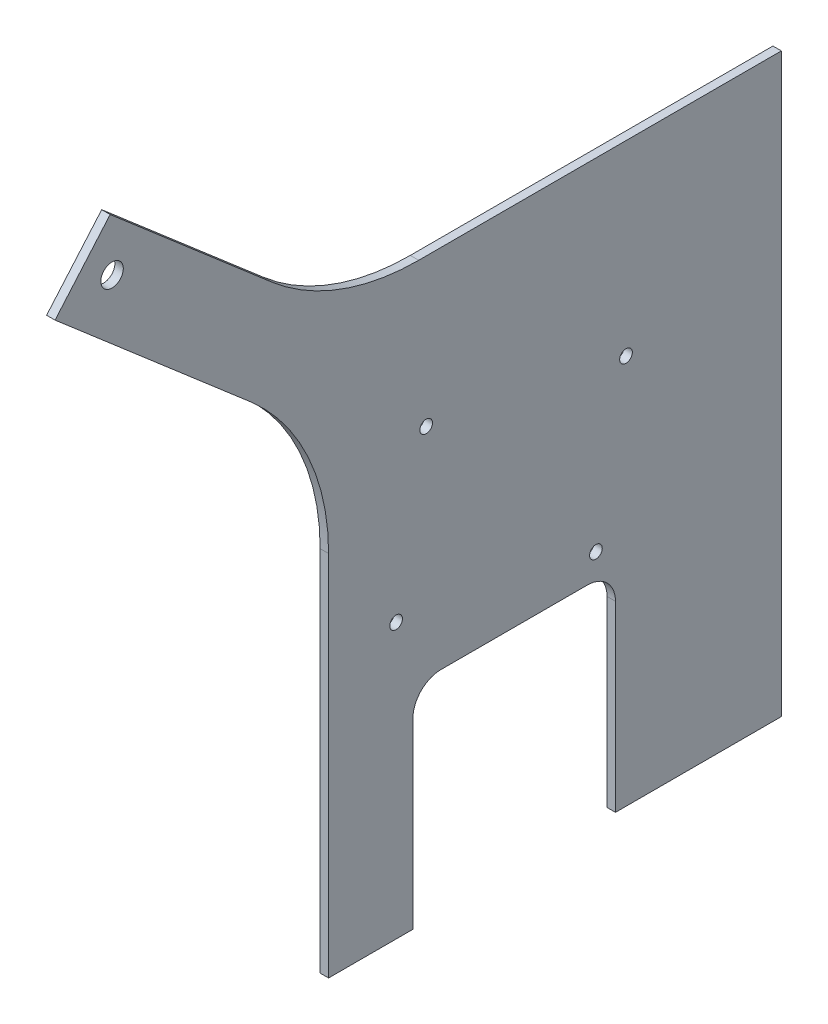
SolidWorks part; units mm, degrees
ref_plane "前视基准面" through (0, 0, 0) normal (0, 0, 1) x (1, 0, 0)
ref_plane "上视基准面" through (0, 0, 0) normal (0, 1, 0) x (1, 0, 0)
ref_plane "右视基准面" through (0, 0, 0) normal (1, 0, 0) x (0, 0, -1)
sketch "草图1" plane through (0, 0, 0) normal (1, 0, 0) x (0, 0, -1)
  line L0 (-27.7697, 191.3174) -> (-97.2699, 251.2218)
  line L1 (0, 0) -> (161, 0)
  line L2 (0, 0) -> (0, 130.7204)
  line L3 (32.0254, 205) -> (161, 205)
  line L4 (161, 0) -> (161, 205)
  line L5 (-97.2699, 251.2218) -> (-77.6836, 273.9456)
  line L6 (-77.6836, 273.9456) -> (-20.2049, 224.403)
  arc A0 (32.0254, 205) -> (-20.2049, 224.403) centre (32.0254, 285) cw
  arc A1 (0, 130.7204) -> (-27.7697, 191.3174) centre (-80, 130.7204) ccw
  circle A2 centre (-77, 255) radius 4
  dimension "D3" = 80
  dimension "D6" = 8
  dimension "D1" = 205
  dimension "D2" = 161
  dimension "D4" = 77
  dimension "D5" = 255
  dimension "D7" = 30
extrude "凸台-拉伸1" add sketch "草图1" along normal mid plane 3
sketch "草图2" plane through (1.5, 0, 0) normal (1, 0, 0) x (0, 0, -1)
  line L0 (0, 0) -> (161, 0) construction
  line L1 (30, 0) -> (102, 0)
  line L2 (30, 0) -> (30, 65)
  line L3 (40, 75) -> (92, 75)
  line L4 (102, 0) -> (102, 65)
  line L5 (0, 130.7204) -> (0, 0) construction
  arc A0 (92, 75) -> (102, 65) centre (92, 65) cw
  arc A1 (40, 75) -> (30, 65) centre (40, 65) ccw
  point P10 (102, 75)
  dimension "D4" = 10
  dimension "D1" = 72
  dimension "D2" = 30
  dimension "D3" = 75
extrude "切除-拉伸1" cut sketch "草图2" against normal through all
hole_wizard "M4 间隙孔1" positions "草图4" profile "草图3" hole size "M4" standard "GB"
sketch "草图4" plane through (1.5, 0, 0) normal (1, 0, 0) x (0, 0, -1)
  line L0 (0, 0) -> (30, 0) construction
  line L1 (0, 130.7204) -> (0, 0) construction
  line L2 (105.7493, 138.6814) -> (95.0593, 83.7112) construction
  line L4 (34.69, 152.5002) -> (24, 97.53) construction
  line L6 (24, 97.53) -> (95.0593, 83.7112) construction
  point P0 (34.69, 152.5002)
  point P1 (24, 97.53)
  point P3 (105.7493, 138.6814)
  point P5 (95.0593, 83.7112)
  dimension "D1" = 56
  dimension "D2" = 97.53
  dimension "D3" = 24
  dimension "D4" = 34.69
sketch "草图3" plane through (1.5, 152.5002, -34.69) normal (0, 1, 0) x (0, 0, -1)
  line L0 (0, 0) -> (0, 5.3519)
  line L1 (0, 5.3519) -> (2.25, 4)
  line L2 (2.25, 4) -> (2.25, 0)
  line L5 (2.25, 0) -> (0, 0)
  line L10 (0, 5.3519) -> (-2.25, 4) construction
  line L11 (0, -6.35) -> (0, 107.95) construction
  dimension "孔直径" = 4.5
  dimension "孔深度" = 4
  dimension "导头角度" = 118
